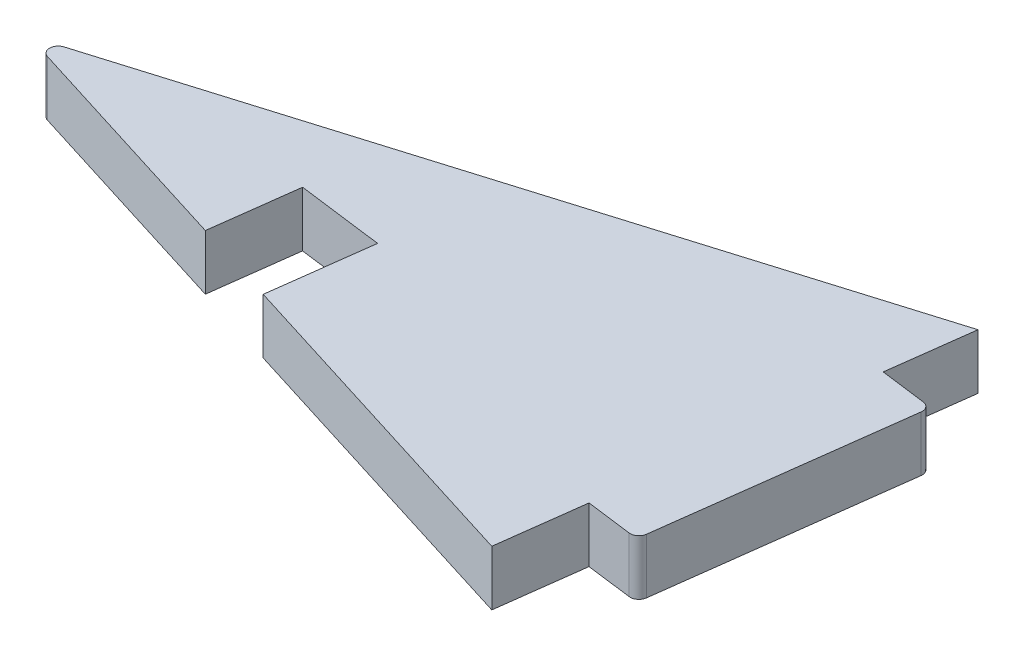
SolidWorks part; units mm, degrees
material "Balsa"
ref_plane "Front Plane" through (0, 0, 0) normal (0, 0, 1) x (1, 0, 0)
ref_plane "Top Plane" through (0, 0, 0) normal (0, 1, 0) x (1, 0, 0)
ref_plane "Right Plane" through (0, 0, 0) normal (1, 0, 0) x (0, 0, -1)
sketch "Sketch1" plane through (0, 0, 0) normal (0, 1, 0) x (1, 0, 0)
  line L0 (-2.5866, -0.183) -> (-1.3066, 9.7348)
  line L1 (3.8134, 49.4057) -> (-80.123, 24.0471)
  line L2 (-80.123, 24.0471) -> (-50.5622, 14.8094)
  line L3 (2.5652, 39.7347) -> (8.8628, 38.922)
  line L4 (8.8628, 38.922) -> (4.9911, 8.922)
  line L5 (4.9911, 8.922) -> (-1.3066, 9.7348)
  line L6 (2.5652, 39.7347) -> (3.8134, 49.4057)
  line L7 (-50.5622, 14.8094) -> (-49.2822, 24.7271)
  line L8 (-49.2822, 24.7271) -> (-39.3645, 23.4471)
  line L9 (-39.3645, 23.4471) -> (-40.8702, 11.7806)
  line L10 (-40.8702, 11.7806) -> (-2.5866, -0.183)
  point P5 (0, 0)
  point P10 (0, 0)
  point P11 (-1.9466, 4.7759)
  dimension "D1" = 50
  dimension "D2" = 80
  dimension "D3" = 80
  dimension "D4" = 6.3498
  dimension "D5" = 30
  dimension "D6" = 6.35
  dimension "D7" = 10
  dimension "D8" = 10
  dimension "D9" = 10
  dimension "D10" = 39.5
extrude "Boss-Extrude1" add sketch "Sketch1" along normal blind 6.35
fillet "Fillet1" radius 1 3 edges at (4.9911, 3.175, -8.922) (8.8628, 3.175, -38.922) (-80.123, 3.175, -24.0471)
